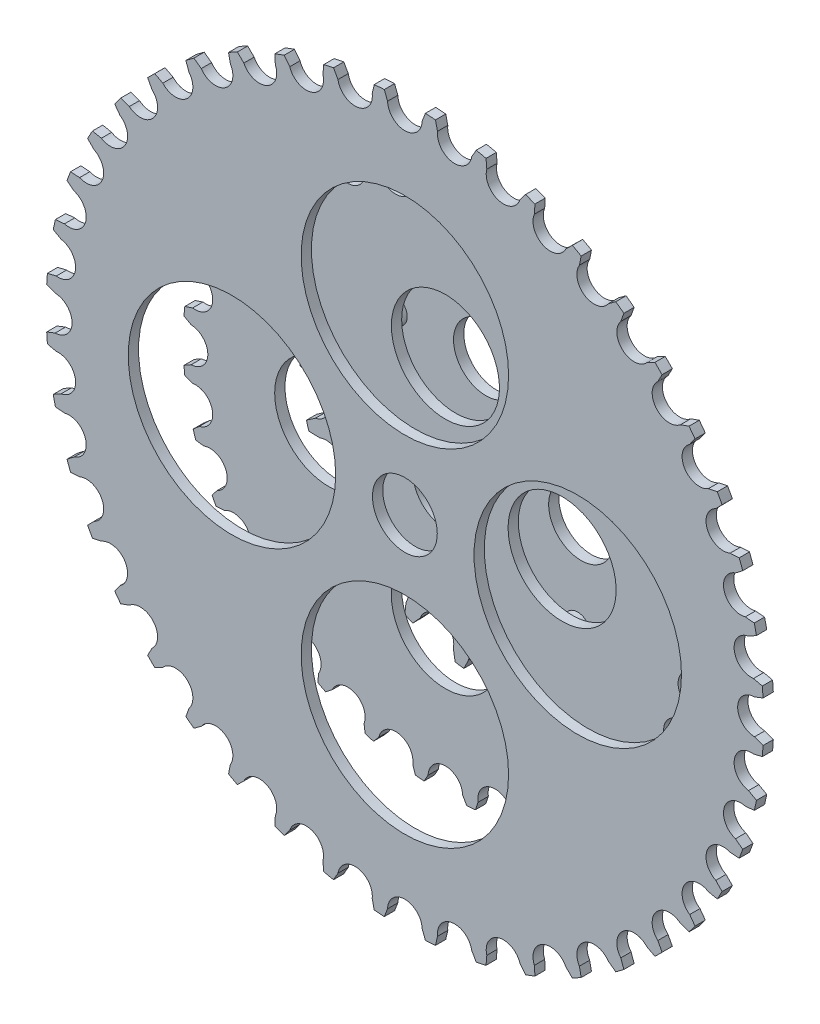
SolidWorks part; units mm, degrees
ref_plane "Ön Düzlem" through (0, 0, 0) normal (0, 0, 1) x (1, 0, 0)
ref_plane "Üst Düzlem" through (0, 0, 0) normal (0, 1, 0) x (1, 0, 0)
ref_plane "Sağ Düzlem" through (0, 0, 0) normal (1, 0, 0) x (0, 0, -1)
sketch "Çizim1" plane through (0, 0, 0) normal (0, 0, 1) x (1, 0, 0)
  circle A0 centre (0, 0) radius 83
  dimension "D1" = 166
extrude "Yükseklik-Ekstrüzyon1" add sketch "Çizim1" along normal blind 2.38
sketch "Çizim2" plane through (0, 0, 2.38) normal (0, 0, 1) x (1, 0, 0)
  line L0 (0, 0) -> (0, 83) construction
  line L1 (0, 0) -> (6.139, 85.8326) construction
  line L3 (5.139, 83.8427) -> (3.9988, 80.9012)
  line L4 (-5.139, 83.8427) -> (-3.9988, 80.9012)
  circle A0 centre (0, 0) radius 83 construction
  arc A1 (-3.9988, 80.9012) -> (3.9988, 80.9012) centre (0, 81) ccw
  circle A45 centre (0, 0) radius 81 construction
  arc A46 (5.139, 83.8427) -> (-5.139, 83.8427) centre (0, 0) ccw
  dimension "D1" = 8
  dimension "D4" = 84
  dimension "D5" = 162
  dimension "D2" = 4.091
  dimension "D3" = 1
extrude "Kes-Ekstrüzyon1" cut sketch "Çizim2" against normal up to next
pattern_circular "Dairesel Çoğaltma1" count 44 over 360 about axis through (0, 0, 2.38) along (0, 0, 1) of "Kes-Ekstrüzyon1"
sketch "Çizim3" plane through (0, 0, 2.38) normal (0, 0, 1) x (1, 0, 0)
  line L1 (0, 0) -> (0, 40) construction
  circle A0 centre (0, 40) radius 24
  circle A2 centre (0, 0) radius 64 construction
  circle A3 centre (0, 0) radius 7.5
  dimension "D2" = 48
  dimension "D5" = 15
  dimension "D1" = 40
extrude "Kes-Ekstrüzyon2" cut sketch "Çizim3" against normal up to next
pattern_circular "Dairesel Çoğaltma2" count 4 over 360 about axis through (0, 0, 2.38) along (0, 0, 1) of "Kes-Ekstrüzyon2"
sketch "Çizim4" plane through (0, 0, 0) normal (0, 0, -1) x (-1, 0, 0)
  line L0 (0, 0) -> (0, 64) construction
  line L1 (0, 0) -> (35.3553, 35.3553)
  circle A0 centre (0, 40) radius 24 construction
  circle A1 centre (35.3553, 35.3553) radius 2.5
  dimension "D2" = 5
  dimension "D1" = 45
  dimension "D3" = 50
extrude "Yükseklik-Ekstrüzyon2" add sketch "Çizim4" along normal blind 7 contours A1
pattern_circular "Dairesel Çoğaltma3" count 4 over 360 about axis through (0, 0, 0) along (0, 0, -1) of "Yükseklik-Ekstrüzyon2"
sketch "Çizim5" plane through (0, 0, -7) normal (0, 0, -1) x (-1, 0, 0)
  circle A0 centre (0, 0) radius 58.9693 construction
  circle A1 centre (0, 0) radius 60.685
  dimension "D1" = 117.9386
  dimension "D2" = 121.37
extrude "Yükseklik-Ekstrüzyon3" add sketch "Çizim5" along normal blind 2.38
sketch "Çizim6" plane through (0, 0, -9.38) normal (0, 0, -1) x (-1, 0, 0)
  line L0 (0, 0) -> (0, 60.685) construction
  line L1 (0, 0) -> (5.9482, 60.3928) construction
  line L2 (3.9975, 58.8281) -> (4.9482, 60.4829)
  line L3 (-3.9975, 58.8281) -> (-4.9482, 60.4829)
  circle A0 centre (0, 0) radius 60.685 construction
  arc A1 (-3.9975, 58.8281) -> (3.9975, 58.8281) centre (0, 58.9693) ccw
  circle A2 centre (0, 0) radius 58.9693 construction
  arc A3 (4.9482, 60.4829) -> (-4.9482, 60.4829) centre (0, 0) ccw
  dimension "D1" = 8
  dimension "D2" = 5.625
  dimension "D3" = 1
extrude "Kes-Ekstrüzyon3" cut sketch "Çizim6" against normal up to next
pattern_circular "Dairesel Çoğaltma4" count 32 over 360 about axis through (0, 0, -9.38) along (0, 0, -1) of "Kes-Ekstrüzyon3"
sketch "Çizim7" plane through (0, 0, -9.38) normal (0, 0, -1) x (-1, 0, 0)
  circle A0 centre (0, 27) radius 12.5
  circle A1 centre (27, 0) radius 12.5
  circle A2 centre (0, -27) radius 12.5
  circle A3 centre (-27, 0) radius 12.5
  dimension "D1" = 25
  dimension "D2" = 27
extrude "Kes-Ekstrüzyon4" cut sketch "Çizim7" against normal up to next
sketch "Çizim8" plane through (0, 0, -9.38) normal (0, 0, -1) x (-1, 0, 0)
  line L0 (0, 0) -> (21.2132, 21.2132) construction
  line L1 (0, 0) -> (0, 39.5) construction
  circle A0 centre (21.2132, 21.2132) radius 3
  circle A1 centre (0, 27) radius 12.5 construction
  circle A2 centre (21.2132, -21.2132) radius 3
  circle A3 centre (-21.2132, -21.2132) radius 3
  circle A4 centre (-21.2132, 21.2132) radius 3
  dimension "D1" = 6
  dimension "D2" = 30
  dimension "D3" = 45
extrude "Yükseklik-Ekstrüzyon4" add sketch "Çizim8" along normal blind 7
sketch "Çizim9" plane through (0, 0, -16.38) normal (0, 0, -1) x (-1, 0, 0)
  circle A0 centre (0, 0) radius 40.6142 construction
  circle A1 centre (0, 0) radius 43
  dimension "D1" = 81.2284
  dimension "D2" = 86
extrude "Yükseklik-Ekstrüzyon5" add sketch "Çizim9" along normal blind 2.38
sketch "Çizim12" plane through (0, 0, -18.76) normal (0, 0, -1) x (-1, 0, 0)
  line L0 (0, 0) -> (0, 43) construction
  line L1 (0, 0) -> (6.1195, 42.5623) construction
  line L2 (3.9951, 40.4172) -> (5.1195, 42.6941)
  line L3 (-3.9951, 40.4172) -> (-5.1195, 42.6941)
  circle A0 centre (0, 0) radius 43 construction
  arc A1 (-3.9951, 40.4172) -> (3.9951, 40.4172) centre (0, 40.6142) ccw
  circle A2 centre (0, 0) radius 40.6142 construction
  arc A3 (5.1195, 42.6941) -> (-5.1195, 42.6941) centre (0, 0) ccw
  dimension "D2" = 8
  dimension "D4" = 81.2284
  dimension "D1" = 8.182
  dimension "D3" = 1
extrude "Kes-Ekstrüzyon5" cut sketch "Çizim12" against normal up to next
pattern_circular "Dairesel Çoğaltma5" count 22 over 360 about axis through (0, 0, -18.76) along (0, 0, -1) of "Kes-Ekstrüzyon5"
sketch "Çizim13" plane through (0, 0, -18.76) normal (0, 0, -1) x (-1, 0, 0)
  line L0 (0, 0) -> (0, 22) construction
  line L1 (0, 0) -> (16.7997, 16.7997) construction
  circle A0 centre (0, 22) radius 7.5
  circle A1 centre (22, 0) radius 7.5
  circle A2 centre (0, -22) radius 7.5
  circle A3 centre (-22, 0) radius 7.5
  dimension "D2" = 15
  dimension "D1" = 45
  dimension "D3" = 22
extrude "Kes-Ekstrüzyon6" cut sketch "Çizim13" against normal up to next
sketch "Çizim14" plane through (0, 0, 2.38) normal (0, 0, 1) x (1, 0, 0)
  circle A0 centre (0, 0) radius 7.5
extrude "Kes-Ekstrüzyon7" cut sketch "Çizim14" against normal through all
